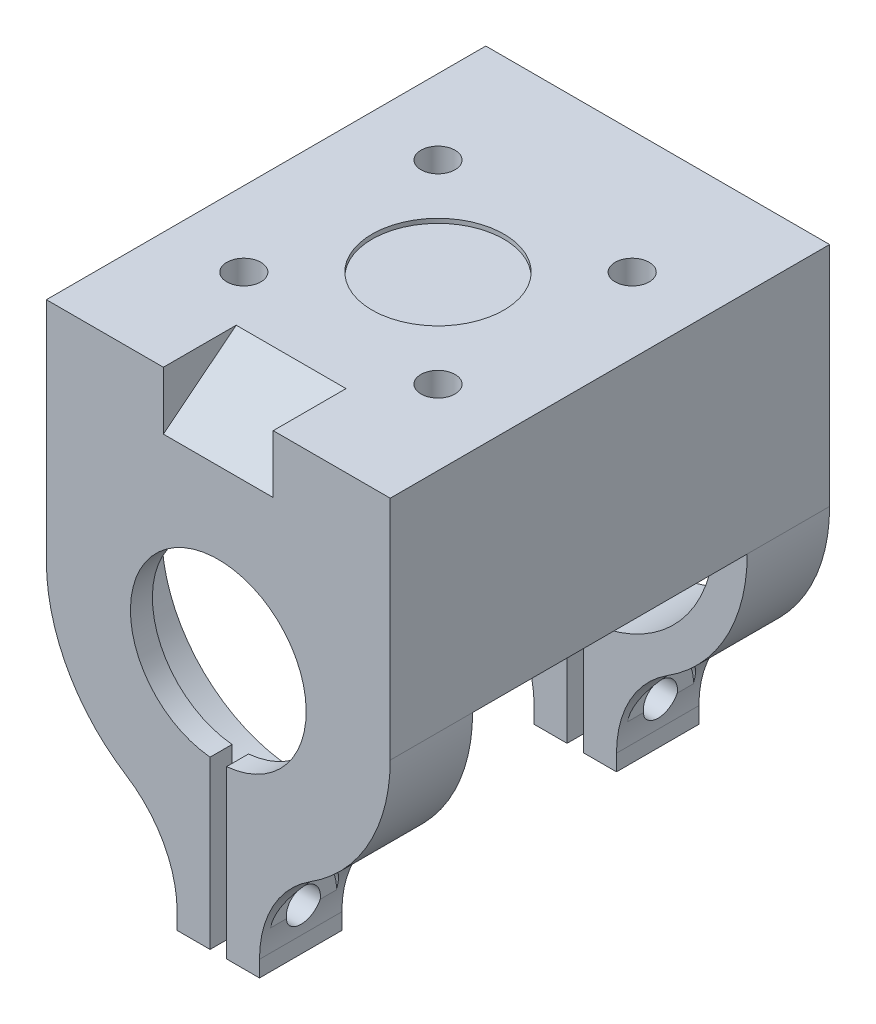
SolidWorks part; units mm, degrees
material "PLA"
ref_plane "Front Plane" through (0, 0, 0) normal (0, 0, 1) x (1, 0, 0)
ref_plane "Top Plane" through (0, 0, 0) normal (0, 1, 0) x (1, 0, 0)
ref_plane "Right Plane" through (0, 0, 0) normal (1, 0, 0) x (0, 0, -1)
sketch "Sketch1" plane through (0, 0, 0) normal (0, 0, 1) x (1, 0, 0)
  line L0 (-15.65, 0) -> (-15.65, 15.65)
  line L1 (-15.65, 15.65) -> (15.65, 15.65)
  line L2 (15.65, 15.65) -> (15.65, 0)
  line L4 (-0.75, -18.6277) -> (0.75, -18.6277)
  line L5 (-0.75, -18.6277) -> (-0.75, -12.6277)
  line L6 (-0.75, -12.6277) -> (0.75, -12.6277)
  line L7 (0.75, -18.6277) -> (0.75, -12.6277)
  line L8 (0, -44.7868) -> (0, 44.7868) construction
  circle A0 centre (0, 0) radius 12.65
  circle A1 centre (0, 0) radius 15.65
  dimension "D1" = 25.3
  dimension "D2" = 31.3
  dimension "D3" = 1.5
  dimension "D4" = 0.75
  dimension "D5" = 6
extrude "Boss-Extrude1" add sketch "Sketch1" along normal mid plane 40 contours A1 L1 L0 | A1 L2 L1 | A1 L5 A0 L7 region at (-12.1543, 12.1543, 0) region at (-10.7533, 10.7533, 0) region at (12.1543, 12.1543, 0)
sketch "Sketch2" plane through (0, 0, 0) normal (0, 0, 1) x (1, 0, 0)
  line L1 (-0.75, -12.6277) -> (-3.75, -12.6277)
  line L2 (-0.75, -12.6277) -> (-0.75, -23.1277)
  line L3 (-0.75, -23.1277) -> (-3.75, -23.1277)
  line L4 (-3.75, -12.6277) -> (-3.75, -23.1277)
  line L5 (0.75, -12.6277) -> (3.75, -12.6277)
  line L6 (0.75, -12.6277) -> (0.75, -23.1277)
  line L7 (0.75, -23.1277) -> (3.75, -23.1277)
  line L8 (3.75, -12.6277) -> (3.75, -23.1277)
  dimension "D1" = 3
  dimension "D2" = 10.5
extrude "Boss-Extrude2" add sketch "Sketch2" along normal mid plane 40
sketch "Sketch4" plane through (0, 15.65, 0) normal (0, 1, 0) x (1, 0, 0)
  line L0 (-15.65, -20) -> (-15.65, 20) construction
  line L1 (-15.65, 20) -> (15.65, 20)
  line L2 (-15.65, 20) -> (-15.65, -20)
  line L3 (-15.65, -20) -> (15.65, -20)
  line L4 (15.65, 20) -> (15.65, -20)
  line L5 (15.65, -20) -> (15.65, 20) construction
  line L6 (-44.2539, 0) -> (44.2539, 0) construction
  line M5 (15.65, 20) -> (-15.65, 20)
  line M6 (-15.65, 20) -> (-15.65, -20)
  line M7 (-15.65, -20) -> (15.65, -20)
  line M8 (15.65, -20) -> (15.65, 20)
  dimension "D1" = 40
  dimension "D2" = 20
extrude "Boss-Extrude3" add sketch "Sketch4" along normal blind 5 contours M8 M5 M6 M7 region at (0, 15.65, 0)
sketch "Sketch5" plane through (15.65, 0, 0) normal (1, 0, 0) x (0, 0, -1)
  line L0 (-20, -23.1277) -> (20, -23.1277) construction
  line L1 (-12.5, 0) -> (12.5, 0)
  line L2 (-12.5, 0) -> (-12.5, -23.1277)
  line L3 (-12.5, -23.1277) -> (12.5, -23.1277)
  line L4 (12.5, 0) -> (12.5, -23.1277)
  line L5 (0, 44.2539) -> (0, -44.2539) construction
  line L7 (55, 0) -> (-55, 0) construction
  point P8 (0, 0)
  point P9 (0, 0)
  dimension "D1" = 25
  dimension "D2" = 12.5
extrude "Cut-Extrude2" cut sketch "Sketch5" along direction (-1, 0, 0) on the side against the normal offset from surface (13.65 mm away) 2 up to plane "Right Plane"
sketch "Sketch6" plane through (0, 20.65, 0) normal (0, 1, 0) x (1, 0, 0)
  line L0 (-44.2539, 0) -> (44.2539, 0) construction
  line L1 (-8.8388, 8.8388) -> (8.8388, 8.8388) construction
  line L2 (-8.8388, 8.8388) -> (-8.8388, -8.8388) construction
  line L3 (-8.8388, -8.8388) -> (8.8388, -8.8388) construction
  line L4 (8.8388, 8.8388) -> (8.8388, -8.8388) construction
  line L5 (0, -44.7868) -> (0, 44.7868) construction
  circle A0 centre (-8.8388, 8.8388) radius 1.55
  circle A1 centre (8.8388, 8.8388) radius 1.55
  circle A2 centre (8.8388, -8.8388) radius 1.55
  circle A3 centre (-8.8388, -8.8388) radius 1.55
  point P6 (-8.8388, 0)
  point P7 (0, 8.8388)
  dimension "D1" = 25
  dimension "D2" = 3.1
extrude "MotorMountHoles" cut sketch "Sketch6" against normal up to surface (20.65 mm away) up to face at (14.15, 0, 0)
sketch "Sketch7" plane through (0, 0, 0) normal (0, -1, 0) x (1, 0, 0)
  circle A0 centre (8.8388, 8.8388) radius 2.55
  dimension "D1" = 5.1
extrude "M3ScrewHeadGuide" [suppressed] add sketch "Sketch7" along normal blind 3
sketch "Sketch8" plane through (-3.75, 0, 0) normal (-1, 0, 0) x (0, 0, 1)
  line L1 (20, -15.1941) -> (20, -23.1277) construction
  line L2 (20, -15.1941) -> (-20, -15.1941) construction
  line L3 (-12.5, -23.1277) -> (-12.5, -15.1941) construction
  line L4 (20, -15.1941) -> (-20, -15.1941) construction
  circle A0 centre (16.25, -19.1941) radius 1.55
  circle A1 centre (-16.25, -19.1941) radius 1.55
  dimension "D1" = 3.1
  dimension "D2" = 3.75
  dimension "D3" = 4
  dimension "D4" = 3.75
  dimension "D5" = 4
extrude "ClampHoles" cut sketch "Sketch8" against normal up to surface (7.5 mm away) up to face at (3.75, -19.1609, 16.25)
sketch "Sketch9" plane through (0, 0, 20) normal (0, 0, 1) x (1, 0, 0)
  line L1 (-0.75, -12.6277) -> (0.75, -12.6277)
  line L2 (-0.75, -12.6277) -> (-0.75, -7.9648)
  line L3 (-0.75, -7.9648) -> (0.75, -7.9648)
  line L4 (0.75, -12.6277) -> (0.75, -7.9648)
  circle A0 centre (0, 0) radius 12.65
  circle A1 centre (0, 0) radius 8
  arc M13 (-0.75, -12.6277) -> (0.75, -12.6277) centre (0, 0) cw
  dimension "D1" = 16
  dimension "D2" = 25.3
extrude "EndStopper" add sketch "Sketch9" against normal blind 2 contours A1 L4 L2 M13 region at (-8.4304, 8.946, 20)
sketch "Sketch10" plane through (0, 0, 0) normal (1, 0, 0) x (0, 0, -1)
  line L0 (55, 0) -> (-55, 0) construction
  line L1 (-12.5, 0) -> (12.5, 0)
  line L2 (-12.5, 0) -> (-12.5, -23.1277)
  line L3 (-12.5, -23.1277) -> (12.5, -23.1277)
  line L4 (12.5, 0) -> (12.5, -23.1277)
  point P6 (12.5, 2.3969)
  point P7 (0, 0)
extrude "Cut-Extrude7" cut sketch "Sketch10" along normal offset from surface (13.65 mm away) 2 from surface up to plane "Right Plane" starting at face at (-15.65, 10.325, 0)
sketch "Sketch11" plane through (-2, 0, 0) normal (-1, 0, 0) x (0, 0, 1)
  line L1 (-12.5, -12.4909) -> (12.5, -12.4909)
  line L2 (-12.5, -12.4909) -> (-12.5, -23.1277)
  line L3 (-12.5, -23.1277) -> (12.5, -23.1277)
  line L4 (12.5, -12.4909) -> (12.5, -23.1277)
extrude "Cut-Extrude8" cut sketch "Sketch11" against normal up to surface (4 mm away) up to face at (2, -17.8093, 0)
fillet "Fillet1" radius 10 4 edges at (-3.75, -15.1941, -16.25) (3.75, -15.1941, 16.25) (3.75, -15.1941, -16.25) (-3.75, -15.1941, 16.25)
sketch "Sketch12" plane through (0, 0, 0) normal (1, 0, 0) x (0, 0, -1)
  line L0 (-30.459, 12.329) -> (0, 36.5616) construction
  line L1 (0, 44.2539) -> (0, -44.2539) construction
  line L2 (-10.1062, 43.5673) -> (4.6194, 25.058) construction
  line L3 (0, 36.5616) -> (-30.459, 12.329)
ref_plane "Plane1" through (0, 11.9634, -15.0373) normal (0, 0.6226, -0.7826) x (-1, 0, 0)
sketch "Sketch13" plane through (0, 11.9634, -15.0373) normal (0, 0.6226, -0.7826) x (-1, 0, 0)
  line L0 (0, 44.7868) -> (0, -44.7868) construction
  line L1 (-5, 34.4844) -> (5, 34.4844)
  line L2 (-5, 34.4844) -> (-5, 24.4844)
  line L3 (-5, 24.4844) -> (5, 24.4844)
  line L4 (5, 34.4844) -> (5, 24.4844)
  dimension "D1" = 10
  dimension "D2" = 10
  dimension "D3" = 5
sweep "Cut-Sweep1" cut profiles "Sketch13" path "Sketch12"
sketch "Sketch15" plane through (0, 0, 0) normal (1, 0, 0) x (0, 0, -1)
  circle A0 centre (16.25, -19.1941) radius 3
  dimension "D1" = 6
extrude "Cut-Extrude10" cut sketch "Sketch15" along normal up to surface (0.0571 mm away) from offset 4 contours A0 up to face at (5.528, -17.1346, -16.25)
sketch "Sketch16" plane through (0, 0, 0) normal (1, 0, 0) x (0, 0, -1)
  line L0 (12.5, -23.1277) -> (20, -23.1277) construction
  line L1 (12.9591, -19.1941) -> (14.6046, -22.0441)
  line L2 (14.6046, -22.0441) -> (17.8954, -22.0441)
  line L3 (17.8954, -22.0441) -> (19.5409, -19.1941)
  line L4 (19.5409, -19.1941) -> (17.8954, -16.3441)
  line L5 (17.8954, -16.3441) -> (14.6046, -16.3441)
  line L6 (14.6046, -16.3441) -> (12.9591, -19.1941)
  circle A0 centre (16.25, -19.1941) radius 2.85 construction
  dimension "D1" = 5.7
extrude "Cut-Extrude11" cut sketch "Sketch16" against normal blind 3 from offset 4 offset against normal yes
mirror "Mirror1" about plane through (0, 0, 0) normal (0, 0, 1) of "Cut-Extrude10", "Cut-Extrude11"
sketch "Sketch17" plane through (0, 20.65, 0) normal (0, 1, 0) x (1, 0, 0)
  circle A0 centre (0, 0) radius 6
  dimension "D1" = 12
extrude "Shaft Clearance" cut sketch "Sketch17" against normal blind 0.4
sketch "Sketch20" plane through (0, 0, 0) normal (0, 1, 0) x (1, 0, 0)
  circle A0 centre (-8.8388, 8.8388) radius 2.8
  circle A1 centre (8.8388, 8.8388) radius 2.8
  circle A2 centre (8.8388, -8.8388) radius 2.8
  circle A3 centre (-8.8388, -8.8388) radius 2.8
  dimension "D1" = 5.6
extrude "Cut-Extrude13" cut sketch "Sketch20" along normal offset from surface (14.65 mm away) 6 up to face at (0, 20.65, 6)
equation "\"InnerDiam\"=25.3"
equation "\"D1@Sketch1\"=\"InnerDiam\""
equation "\"OuterDiam\"=31.3"
equation "\"D2@Sketch1\"=\"OuterDiam\""
equation "\"TightenGap\"=1.5"
equation "\"D3@Sketch1\"=\"TightenGap\""
equation "\"D4@Sketch1\"=\"TightenGap\"/2"
equation "\"D5@Sketch1\"=\"OuterDiam\"-\"InnerDiam\""
equation "\"ClampLen\"=10.5"
equation "\"D2@Sketch2\"=\"ClampLen\""
equation "\"Thick\"=40"
equation "\"D1@Boss-Extrude2\"=\"Thick\""
equation "\"D1@Boss-Extrude1\"=\"Thick\""
equation "\"MotBaseThick\"=5"
equation "\"D1@Boss-Extrude3\"=\"MotBaseThick\""
equation "\"TopPlateLen\"=35"
equation "\"D1@Sketch4\"=\"Thick\""
equation "\"D2@Sketch4\"=\"Thick\"/2"
equation "\"D1@Sketch5\"=\"Thick\"- 2 * \"ClampWidth\""
equation "\"D2@Sketch5\"=(\"Thick\"- 2 * \"ClampWidth\")/2"
equation "\"MotorMountDiam\"=25"
equation "\"D1@Sketch6\"=\"MotorMountDiam\""
equation "\"ClampWidth\"= 7.5"
equation "\"D2@Sketch8\"=\"ClampWidth\"/2"
equation "\"D3@Sketch8\"=(\"ClampLen\"- 2.5)/2"
equation "\"D4@Sketch8\"=\"ClampWidth\"/2"
equation "\"D5@Sketch8\"=(\"ClampLen\"- 2.5)/2"
equation "\"D2@Sketch9\"=\"InnerDiam\""
equation "\"D19@Cut-Extrude2\"=\"OuterDiam\"/2"
equation "\"HHeadWid\"=5.6"
equation "\"D1@Sketch20\"=\"HHeadWid\""
